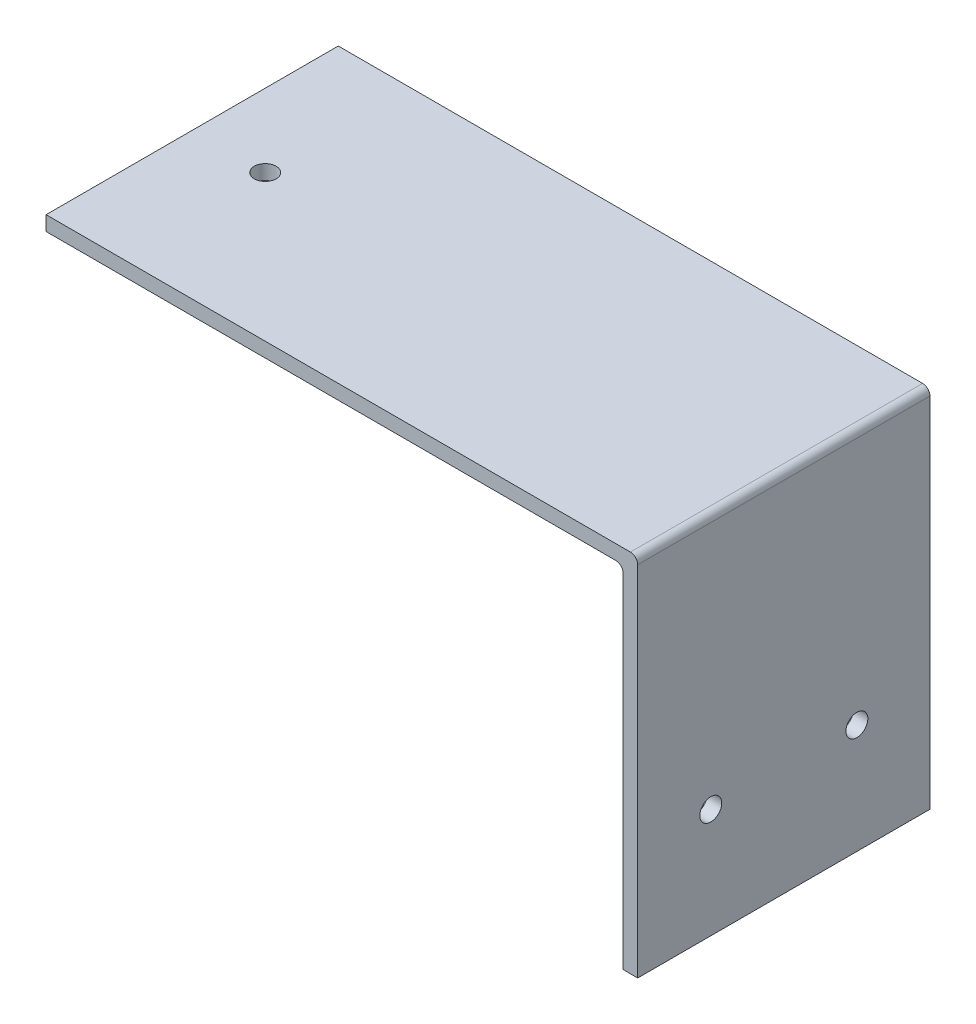
SolidWorks part; units mm, degrees
ref_plane "Front Plane" through (0, 0, 0) normal (0, 0, 1) x (1, 0, 0)
ref_plane "Top Plane" through (0, 0, 0) normal (0, 1, 0) x (1, 0, 0)
ref_plane "Right Plane" through (0, 0, 0) normal (1, 0, 0) x (0, 0, -1)
sketch "Sketch1" plane through (0, 0, 0) normal (0, 1, 0) x (1, 0, 0)
  line L1 (0, 0) -> (80, 0)
  line L2 (0, 0) -> (0, 40)
  line L3 (0, 40) -> (80, 40)
  line L4 (80, 0) -> (80, 40)
  circle A0 centre (10, 20) radius 1.5
  dimension "D3" = 10
  dimension "D4" = 20
  dimension "D1" = 40
  dimension "D2" = 80
extrude "Boss-Extrude1" add sketch "Sketch1" along normal blind 2
sketch "Sketch2" plane through (0, 2, 0) normal (0, 1, 0) x (1, 0, 0)
  line L0 (80, 40) -> (0, 40) construction
  line L1 (80, 0) -> (79, 0)
  line L2 (80, 0) -> (80, 40)
  line L3 (80, 40) -> (79, 40)
  line L4 (79, 0) -> (79, 40)
  line L6 (80, 0) -> (81, 0)
  line L7 (80, 0) -> (80, 40)
  line L8 (80, 40) -> (81, 40)
  line L9 (81, 0) -> (81, 40)
  line M2 (0, 0) -> (80, 0)
  line M3 (80, 0) -> (80, 40)
  line M4 (80, 40) -> (0, 40)
  dimension "D1" = 1
  dimension "D2" = 1
extrude "Boss-Extrude2" add sketch "Sketch2" against normal blind 50 contours L4 M2 M3 M4 | L6 L9 L8 M3 region at (79.5, 2, -20) region at (80.5, 2, -20)
sketch "Sketch3" plane through (79, 0, 0) normal (-1, 0, 0) x (0, 0, 1)
  line L0 (-40, -48) -> (-40, 0) construction
  line L1 (0, -48) -> (-40, -48) construction
  line L2 (0, -48) -> (0, 0) construction
  circle A0 centre (-30, -33) radius 1.5
  circle A1 centre (-10, -33) radius 1.5
  dimension "D1" = 3
  dimension "D2" = 3
  dimension "D3" = 10
  dimension "D4" = 15
  dimension "D5" = 10
  dimension "D6" = 15
extrude "Cut-Extrude1" cut sketch "Sketch3" against normal blind 70
fillet "Fillet1" radius 1 2 edges at (79, 0, -20) (81, 2, -20)
